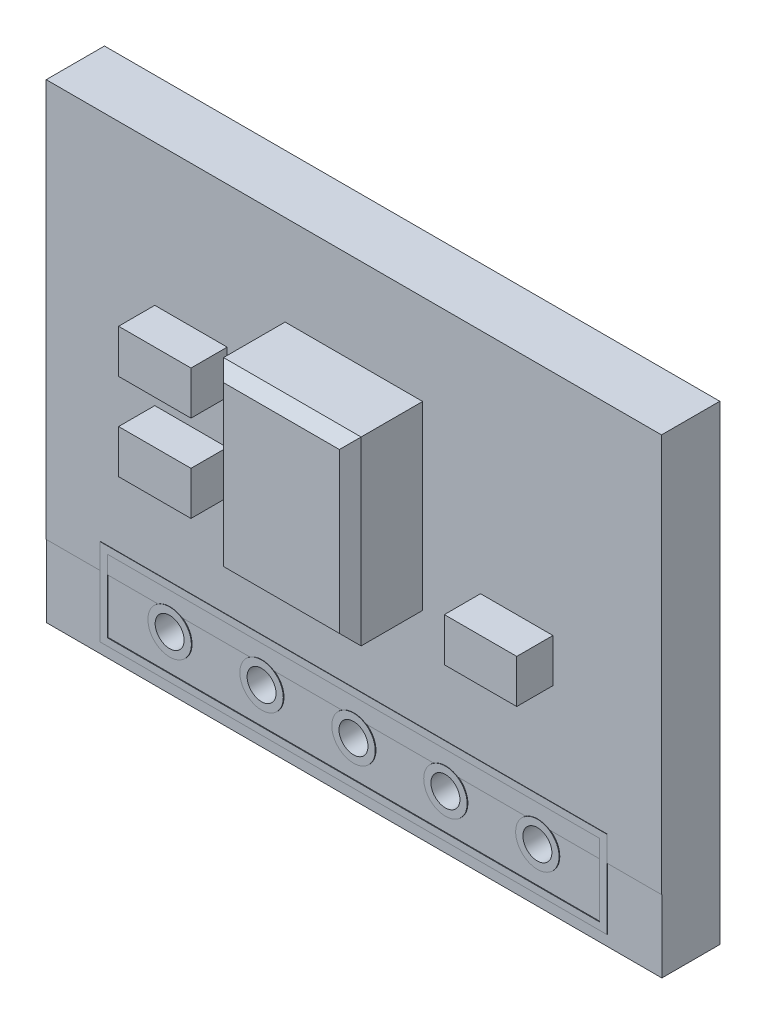
SolidWorks part; units mm, degrees
ref_plane "Front Plane" through (0, 0, 0) normal (0, 0, 1) x (1, 0, 0)
ref_plane "Top Plane" through (0, 0, 0) normal (0, 1, 0) x (1, 0, 0)
ref_plane "Right Plane" through (0, 0, 0) normal (1, 0, 0) x (0, 0, -1)
sketch "Sketch1" plane through (0, 0, 0) normal (0, 0, 1) x (1, 0, 0)
  line L0 (-11.5, 9.5) -> (-9.5, 11.5)
  line L1 (-9.5, -11.5) -> (9.5, -11.5)
  line L2 (-11.5, -9.5) -> (-11.5, 9.5)
  line L3 (-9.5, 11.5) -> (9.5, 11.5)
  line L4 (11.5, -9.5) -> (11.5, 9.5)
  line L7 (9.5, 11.5) -> (11.5, 9.5)
  line L8 (9.5, -11.5) -> (11.5, -9.5)
  line L9 (-11.5, -9.5) -> (-9.5, -11.5)
  line L11 (-9, -6) -> (9, -6) construction
  line L12 (-9, -6) -> (-9, 6) construction
  line L13 (-9, 6) -> (9, 6) construction
  line L14 (9, -6) -> (9, 6) construction
  point P0 (0, 0)
  point P1 (0, 11.5)
  point P4 (0, -6)
  point P14 (9, 0)
  point P22 (0, 0)
  dimension "D1" = 23
  dimension "D2" = 23
  dimension "D3" = 2
  dimension "D5" = 2
  dimension "D6" = 11.5
  dimension "D7" = 12
  dimension "D8" = 2.5
extrude "Boss-Extrude1" add sketch "Sketch1" along normal blind 1.6
sketch "Sketch2" plane through (0, 0, 0) normal (0, 0, 1) x (1, 0, 0)
  line L0 (11.5, -9.5) -> (11.5, 9.5) construction
  line L1 (-8.5, -6) -> (8.5, -6)
  line L2 (-8.5, -6) -> (-8.5, 6)
  line L3 (-8.5, 6) -> (8.5, 6)
  line L4 (8.5, -6) -> (8.5, 6)
  line L5 (-8.5, -6) -> (8.5, 6) construction
  line L6 (-8.5, 6) -> (8.5, -6) construction
  line L7 (-9.5, -11.5) -> (9.5, -11.5) construction
  point P0 (0, 0)
  dimension "D1" = 3
  dimension "D2" = 5.5
extrude "Boss-Extrude2" add sketch "Sketch2" along normal blind 1.61
sketch "Sketch3" plane through (0, 0, 0) normal (0, 0, 1) x (1, 0, 0)
  line L0 (0, -5.3) -> (0, -7.7) construction
  line L1 (-7, -7.7) -> (7, -7.7)
  line L2 (-7, -7.7) -> (-7, -5.3)
  line L3 (-7, -5.3) -> (7, -5.3)
  line L4 (7, -7.7) -> (7, -5.3)
  line L5 (-7, -7.7) -> (7, -5.3) construction
  line L6 (-7, -5.3) -> (7, -7.7) construction
  line L7 (-6.8, -5.5) -> (6.8, -5.5)
  line L8 (6.8, -7.5) -> (6.8, -5.5)
  line L9 (-6.8, -7.5) -> (6.8, -7.5)
  line L10 (-6.8, -7.5) -> (-6.8, -5.5)
  circle A0 centre (0, -6.5) radius 0.6
  circle A1 centre (2.54, -6.5) radius 0.6
  circle A2 centre (5.08, -6.5) radius 0.6
  circle A3 centre (-5.08, -6.5) radius 0.6
  circle A4 centre (-2.54, -6.5) radius 0.6
  circle A5 centre (-5.08, -6.5) radius 0.4
  circle A6 centre (-2.54, -6.5) radius 0.4
  circle A7 centre (0, -6.5) radius 0.4
  circle A8 centre (2.54, -6.5) radius 0.4
  circle A9 centre (5.08, -6.5) radius 0.4
  point P0 (0, -6.5)
  dimension "D6" = 1.2
  dimension "D1" = 14
  dimension "D2" = 2.4
  dimension "D3" = 6.5
  dimension "D4" = 2.54
  dimension "D5" = 2.54
  dimension "D7" = 0.2
extrude "Boss-Extrude3" add sketch "Sketch3" along normal blind 1.62 contours A1 A8 | A2 A9 | A0 A7 | A4 A6 | A3 A5 | L1 L4 L3 L2 L9 L10 L7 L8 region at (-6.858, -6.5, 0) region at (-0.583, -6.5, 0) region at (1.957, -6.5, 0) region at (4.497, -6.5, 0) region at (-5.663, -6.5, 0) region at (-3.123, -6.5, 0)
extrude "Cut-Extrude1" cut sketch "Sketch3<3>" along normal blind 2.62 contours A5 | A6 | A7 | A8 | A9 region at (-5.08, -6.5, 0) region at (-2.54, -6.5, 0) region at (0, -6.5, 0) region at (2.54, -6.5, 0) region at (5.08, -6.5, 0)
sketch "Sketch3<3>" plane through (0, 0, 0) normal (0, 0, 1) x (1, 0, 0) same geometry as "Sketch3"
sketch "Sketch4" plane through (0, 0, 0) normal (0, 0, 1) x (1, 0, 0)
  line L1 (-1.9, -2.5) -> (1.9, -2.5)
  line L2 (-1.9, -2.5) -> (-1.9, 2.5)
  line L3 (-1.9, 2.5) -> (1.9, 2.5)
  line L4 (1.9, -2.5) -> (1.9, 2.5)
  line L5 (-1.9, -2.5) -> (1.9, 2.5) construction
  line L6 (-1.9, 2.5) -> (1.9, -2.5) construction
  point P0 (0, 0)
  dimension "D1" = 5
  dimension "D2" = 3.8
extrude "Boss-Extrude4" add sketch "Sketch4" along normal blind 2 from surface starting at face at (0, -2.825, 1.61)
sketch "Sketch5" plane through (0, 0, 0) normal (0, 0, 1) x (1, 0, 0)
  line L1 (-5.5001, -1.3) -> (-3.5001, -1.3)
  line L2 (-5.5001, -1.3) -> (-5.5001, -2.5)
  line L3 (-5.5001, -2.5) -> (-3.5001, -2.5)
  line L4 (-3.5001, -1.3) -> (-3.5001, -2.5)
  line L5 (-5.5001, -1.3) -> (-3.5001, -2.5) construction
  line L6 (-5.5001, -2.5) -> (-3.5001, -1.3) construction
  line L7 (-5.5, 1.1) -> (-3.5, 1.1)
  line L8 (-5.5, 1.1) -> (-5.5, -0.1)
  line L9 (-5.5, -0.1) -> (-3.5, -0.1)
  line L10 (-3.5, 1.1) -> (-3.5, -0.1)
  line L11 (-5.5, 1.1) -> (-3.5, -0.1) construction
  line L12 (-5.5, -0.1) -> (-3.5, 1.1) construction
  line L13 (3.5, -1.3) -> (5.5, -1.3)
  line L14 (3.5, -1.3) -> (3.5, -2.5)
  line L15 (3.5, -2.5) -> (5.5, -2.5)
  line L16 (5.5, -1.3) -> (5.5, -2.5)
  line L17 (3.5, -1.3) -> (5.5, -2.5) construction
  line L18 (3.5, -2.5) -> (5.5, -1.3) construction
  line L19 (1.9, -2.5) -> (1.9, 2.5) construction
  line L20 (-1.9, 2.5) -> (-1.9, -2.5) construction
  line L21 (-1.9, -2.5) -> (1.9, -2.5) construction
  point P0 (-4.5001, -1.9)
  point P5 (-4.5, 0.5)
  point P10 (4.5, -1.9)
  dimension "D1" = 1.2
  dimension "D2" = 2
  dimension "D3" = 1.6
  dimension "D4" = 1.6
  dimension "D5" = 1.2
extrude "Boss-Extrude5" add sketch "Sketch5" along normal blind 1 from surface starting at face at (0, -2.825, 1.61)
chamfer "Chamfer1" distance 0.3 angle 45 4 edges at (0, -2.5, 3.61) (-1.9, 0, 3.61) (0, 2.5, 3.61) (1.9, 0, 3.61)
sketch "Sketch8" plane through (0, 0, 0) normal (0, 0, 1) x (1, 0, 0)
  line L0 (13.5, 13) -> (13.5, -13)
  line L1 (8.5, 8) -> (-8.5, 8)
  line L2 (8.5, 8) -> (8.5, -8)
  line L3 (8.5, -8) -> (-8.5, -8)
  line L4 (-8.5, 8) -> (-8.5, -8)
  line L5 (8.5, 8) -> (-8.5, -8) construction
  line L6 (8.5, -8) -> (-8.5, 8) construction
  line L7 (13.5, -13) -> (-13.5, -13)
  line L8 (-13.5, 13) -> (-13.5, -13)
  line L9 (13.5, 13) -> (-13.5, 13)
  point P0 (0, 0)
  dimension "D1" = 16
  dimension "D2" = 17
  dimension "D3" = 5
extrude "Cut-Extrude9" cut sketch "Sketch8" along normal blind 3
sketch "Sketch9" plane through (0, 0, 0) normal (0, 0, 1) x (1, 0, 0)
  line L0 (-8.5, 8) -> (8.5, 8) construction
  line L3 (8.5, 8) -> (7, 8)
  line L5 (8.5, -8) -> (-8.5, -8) construction
  line L6 (-8.5, 8) -> (8.5, 8)
  line L7 (-8.5, 8) -> (-8.5, 5)
  line L8 (-8.5, 5) -> (8.5, 5)
  line L9 (8.5, 8) -> (8.5, 5)
  line L14 (-8.5, 8) -> (-7, 8)
  point P0 (0, 0)
  dimension "D1" = 13
extrude "Cut-Extrude11" cut sketch "Sketch9" along normal blind 2 contours L7 L6 L9 L8
